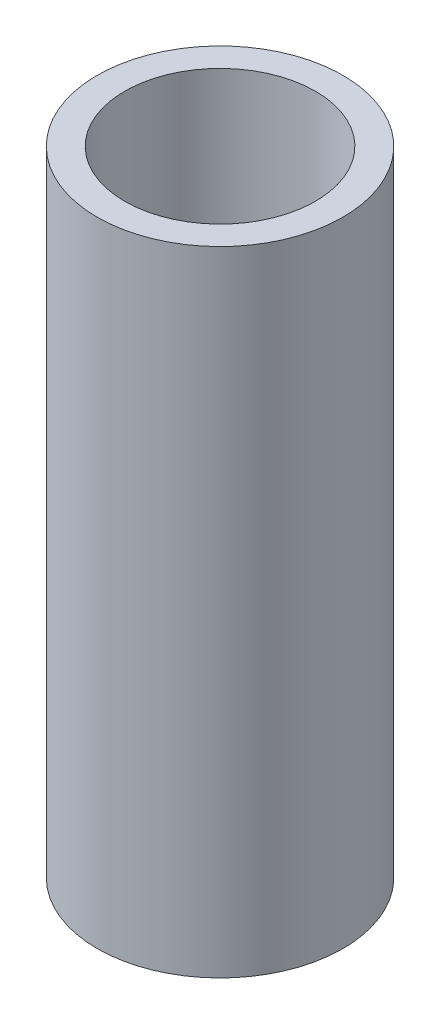
SolidWorks part; units mm, degrees
ref_plane "Front Plane" through (0, 0, 0) normal (0, 0, 1) x (1, 0, 0)
ref_plane "Top Plane" through (0, 0, 0) normal (0, 1, 0) x (1, 0, 0)
ref_plane "Right Plane" through (0, 0, 0) normal (1, 0, 0) x (0, 0, -1)
sketch "Sketch1" plane through (0, 0, 0) normal (0, 1, 0) x (1, 0, 0)
  circle A0 centre (0, 0) radius 15
  dimension "SLEEVE_OD" = 30
extrude "Boss-Extrude1" add sketch "Sketch1" along normal blind 77.3329
sketch "Sketch2" plane through (0, 0, 0) normal (0, 1, 0) x (1, 0, 0)
  circle A0 centre (0, 0) radius 11.6431
  dimension "BORE_D" = 23.2862
extrude "Cut-Extrude1" cut sketch "Sketch2" along normal through all
chamfer "Chamfer1" distance 1.5162 angle 60 rebuild error yes
